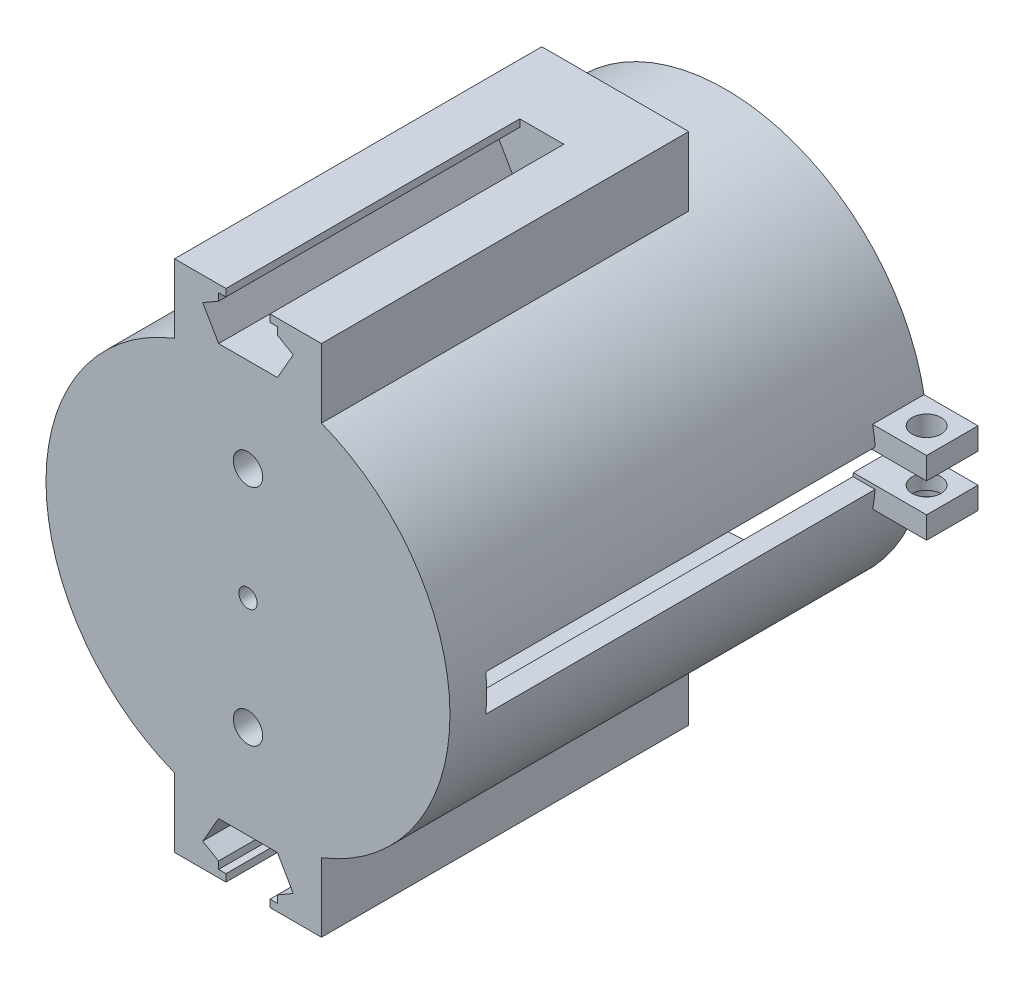
SolidWorks part; units mm, degrees
ref_plane "Front Plane" through (0, 0, 0) normal (0, 0, 1) x (1, 0, 0)
ref_plane "Top Plane" through (0, 0, 0) normal (0, 1, 0) x (1, 0, 0)
ref_plane "Right Plane" through (0, 0, 0) normal (1, 0, 0) x (0, 0, -1)
sketch "Sketch1" plane through (0, 0, 0) normal (0, 0, 1) x (1, 0, 0)
  line L0 (0, 23.495) -> (0, 15.24) construction
  line L1 (23.495, 0) -> (34.925, 0)
  line L2 (-23.495, 0) -> (-34.925, 0)
  line L3 (0, -15.24) -> (0, -23.495) construction
  circle A0 centre (0, 0) radius 23.495
  circle A1 centre (0, 0) radius 15.24
  circle A2 centre (0, 19.3675) radius 2.54
  circle A3 centre (0, -19.3675) radius 2.54
  circle A5 centre (0, 0) radius 34.925
  dimension "D1" = 8.255
  dimension "1.85" = 46.99
  dimension "D2" = 5.08
  dimension "D3" = 69.85
extrude "Boss-Extrude1" add sketch "Sketch1" along normal blind 6.35 contours A0 A3 A2 A1 | L1 A5 L2 A0 | L1 A0 L2 A5 region at (0, 24.2759, 0) region at (0, -22.8305, 0) region at (29.21, -0.7809, 0)
extrude "Boss-Extrude2" add sketch "Sketch1<2>" against normal blind 3.81 and the other way up to surface (6.35 mm away) contours A1 region at (0, 0, 0) other way up to face at (34.925, 0, 6.35)
sketch "Sketch1<2>" plane through (0, 0, 0) normal (0, 0, 1) x (1, 0, 0) same geometry as "Sketch1"
sketch "Sketch3" plane through (0, 0, 6.35) normal (0, 0, 1) x (1, 0, 0)
  circle A0 centre (0, 0) radius 1.5875
  dimension "D1" = 3.175
extrude "Cut-Extrude2" cut sketch "Sketch3" against normal through all
sketch "Sketch4" plane through (0, 0, 0) normal (0, 0, -1) x (-1, 0, 0)
  circle A0 centre (0, 0) radius 28.575
  circle A1 centre (0, 0) radius 34.925 construction
  circle A2 centre (0, 0) radius 34.925
  circle A3 centre (0, 0) radius 31.115
  circle M1 centre (0, 0) radius 34.925
  dimension "D1" = 57.15
  dimension "D2" = 3.81
extrude "Boss-Extrude3" add sketch "Sketch4" along normal blind 76.2 contours A3 M1 region at (33.9372, 0, 0)
sketch "Sketch5" plane through (0, 0, 0) normal (1, 0, 0) x (0, 0, -1)
  line L0 (76.2, -31.115) -> (76.2, 31.115) construction
  line L1 (76.2, 3.175) -> (0, 3.175)
  line L2 (76.2, 3.175) -> (76.2, -3.175)
  line L3 (76.2, -3.175) -> (0, -3.175)
  line L4 (0, 3.175) -> (0, -3.175)
  dimension "D1" = 6.35
extrude "Cut-Extrude3" cut sketch "Sketch5" along normal through all from offset 30.48
sketch "Sketch6" plane through (0, 0, 0) normal (0, 1, 0) x (1, 0, 0)
  line L1 (34.7804, 76.2) -> (43.6704, 76.2)
  line L2 (34.7804, 76.2) -> (34.7804, 67.31)
  line L3 (34.7804, 67.31) -> (43.6704, 67.31)
  line L4 (43.6704, 76.2) -> (43.6704, 67.31)
  circle A0 centre (39.2254, 71.755) radius 2.5
  dimension "D3" = 5
  dimension "D1" = 8.89
  dimension "D2" = 8.89
  dimension "D4" = 4.445
  dimension "D5" = 4.445
extrude "Boss-Extrude4" add sketch "Sketch6" along normal blind 3.81 from offset 2.54 separate body
extrude "Boss-Extrude5" add sketch "Sketch6<2>" against normal blind 3.81 from offset 2.54 separate body offset against normal yes
sketch "Sketch6<2>" plane through (0, 0, 0) normal (0, 1, 0) x (1, 0, 0) same geometry as "Sketch6"
sketch "Sketch8" plane through (34.7804, 0, 0) normal (-1, 0, 0) x (0, 0, 1)
  line L0 (-67.31, -2.54) -> (-76.2, -2.54) construction
  line L1 (-76.2, -2.54) -> (-76.2, -6.35) construction
  line L2 (-76.2, -6.35) -> (-67.31, -6.35) construction
  line L3 (-67.31, -6.35) -> (-67.31, -2.54) construction
  line L4 (-76.2, 2.54) -> (-67.31, 2.54) construction
  line L5 (-67.31, 2.54) -> (-67.31, 6.35) construction
  line L6 (-67.31, 6.35) -> (-76.2, 6.35) construction
  line L7 (-76.2, 6.35) -> (-76.2, 2.54) construction
  line L8 (-67.31, -2.54) -> (-76.2, -2.54)
  line L9 (-76.2, -2.54) -> (-76.2, -6.35)
  line L10 (-76.2, -6.35) -> (-67.31, -6.35)
  line L11 (-67.31, -6.35) -> (-67.31, -2.54)
  line L12 (-76.2, 2.54) -> (-67.31, 2.54)
  line L13 (-67.31, 2.54) -> (-67.31, 6.35)
  line L14 (-67.31, 6.35) -> (-76.2, 6.35)
  line L15 (-76.2, 6.35) -> (-76.2, 2.54)
extrude "Boss-Extrude6" add sketch "Sketch8" along normal up to surface (4.3202 mm away) up to face at (-0.0812, 0, -38.1)
sketch "Sketch9" plane through (0, -6.35, 0) normal (0, -1, 0) x (1, 0, 0)
  circle A0 centre (39.2254, -71.755) radius 2.5 construction
  circle A1 centre (39.2254, -71.755) radius 2.5
  circle A2 centre (39.2254, -71.755) radius 3
  dimension "D1" = 6
extrude "Cut-Extrude4" cut sketch "Sketch9" against normal blind 1.27
ref_plane "Plane1" through (0, -38.1, 0) normal (0, 1, 0) x (1, 0, 0)
sketch "Sketch12" plane through (0, -38.1, 0) normal (0, 1, 0) x (1, 0, 0)
  line L0 (-12.7, -6.35) -> (12.7, -6.35)
  line L1 (-12.7, -6.35) -> (-12.7, 57.15)
  line L2 (-12.7, 57.15) -> (12.7, 57.15)
  line L3 (12.7, -6.35) -> (12.7, 57.15)
  line L4 (0, 57.15) -> (0, -6.35) construction
  line L5 (-34.925, -6.35) -> (34.925, -6.35) construction
  dimension "D1" = 63.5
  dimension "D2" = 25.4
extrude "Boss-Extrude7" add sketch "Sketch12" along normal up to surface and the other way blind 6.35 up to face at (34.925, 0, 6.35)
sketch "Sketch13" plane through (0, 0, 6.35) normal (0, 0, 1) x (1, 0, 0)
  line L0 (-12.7, -44.45) -> (12.7, -44.45) construction
  line L1 (-5.08, -44.45) -> (5.08, -44.45)
  line L2 (-5.08, -44.45) -> (-5.08, -35.56)
  line L3 (-5.08, -35.56) -> (5.08, -35.56)
  line L4 (5.08, -44.45) -> (5.08, -35.56)
  line L5 (-7.8296, -40.3225) -> (-5.08, -41.91)
  line L6 (7.8296, -40.3225) -> (5.08, -35.56)
  line L7 (-5.08, -35.56) -> (-7.8296, -40.3225)
  line L8 (7.8296, -40.3225) -> (5.08, -41.91)
  line L9 (-3.81, -44.45) -> (-3.81, -43.18)
  line L10 (-3.81, -43.18) -> (-5.08, -43.18)
  line L11 (3.81, -44.45) -> (3.81, -43.18)
  line L12 (3.81, -43.18) -> (5.08, -43.18)
  point P6 (0, -44.45)
  line M12 (-12.7, -44.45) -> (12.7, -44.45)
  dimension "D1" = 8.89
  dimension "D2" = 10.16
  dimension "D3" = 30
  dimension "D4" = 30
  dimension "D5" = 2.54
  dimension "D6" = 1.27
  dimension "D7" = 1.27
extrude "Cut-Extrude5" cut sketch "Sketch13" against normal blind 50.8 contours L4 L3 L2 M12 | L8 L6 L4 | L2 L7 L5 region at (0, -39.8639, 6.35) region at (-5.9965, -39.2642, 6.35) region at (5.9965, -39.2642, 6.35)
mirror "Mirror1" about plane through (0, 0, 0) normal (0, 1, 0) of "Cut-Extrude5", "Boss-Extrude7"
